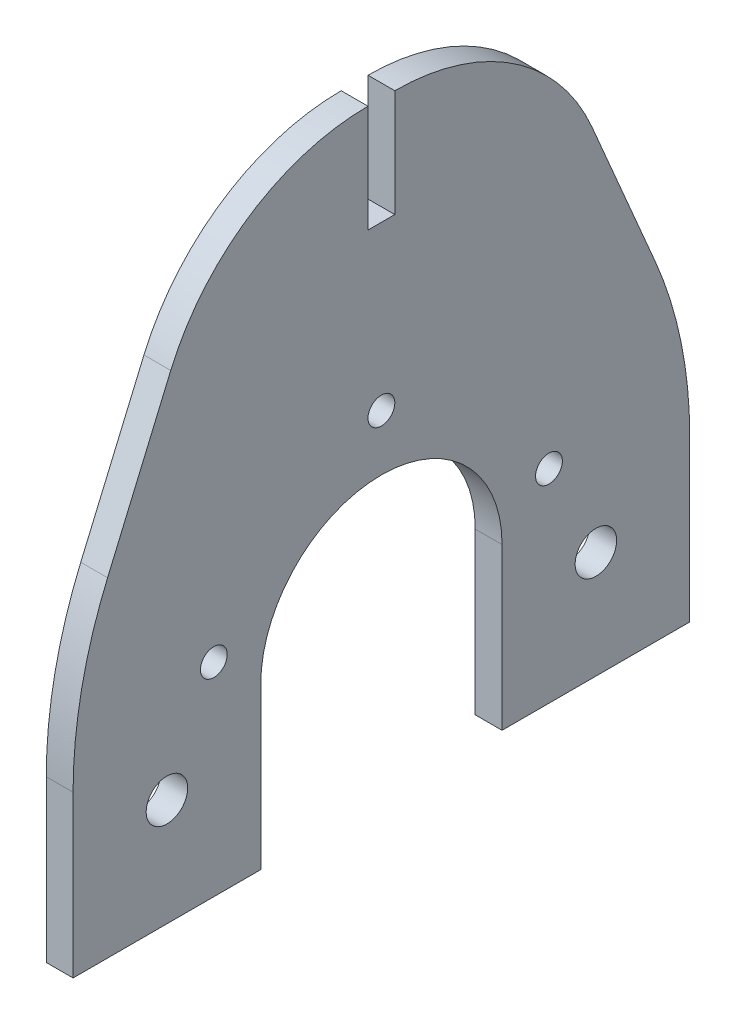
SolidWorks part; units mm, degrees
material "6061 Alloy"
ref_plane "Front Plane" through (0, 0, 0) normal (0, 0, 1) x (1, 0, 0)
ref_plane "Top Plane" through (0, 0, 0) normal (0, 1, 0) x (1, 0, 0)
ref_plane "Right Plane" through (0, 0, 0) normal (1, 0, 0) x (0, 0, -1)
sketch "Sketch1" plane through (0, 0, 0) normal (1, 0, 0) x (0, 0, -1)
  line L0 (1.5875, 52.8963) -> (1.5875, 40.1963)
  line L1 (1.5875, 40.1963) -> (-1.5875, 40.1963)
  line L2 (0, 0) -> (0, 73.524) construction
  line L3 (-1.5875, 52.8963) -> (-1.5875, 40.1963)
  line L4 (25.4, 0) -> (-25.4, 0) construction
  line L5 (24.9457, 37.4739) -> (32.429, 19.9553)
  line L6 (-24.9457, 37.4739) -> (-32.429, 19.9553)
  line L7 (36.5125, 0) -> (36.5125, -19.05)
  line L8 (36.5125, -19.05) -> (14.2875, -19.05)
  line L9 (14.2875, -19.05) -> (14.2875, 0)
  line L10 (-14.2875, 0) -> (-14.2875, -19.05)
  line L11 (-14.2875, -19.05) -> (-36.5125, -19.05)
  line L12 (-36.5125, -19.05) -> (-36.5125, 0)
  arc A0 (14.2875, 0) -> (-14.2875, 0) centre (0, 0) ccw
  arc A3 (36.5125, 0) -> (32.429, 19.9553) centre (-14.2875, 0) ccw
  arc A5 (24.9457, 37.4739) -> (1.5875, 52.8963) centre (1.5875, 27.4963) ccw
  arc A7 (-36.5125, 0) -> (-32.429, 19.9553) centre (14.2875, 0) cw
  arc A10 (-24.9457, 37.4739) -> (-1.5875, 52.8963) centre (-1.5875, 27.4963) cw
  circle A11 centre (25.4, 0) radius 2.5797 construction
  circle A12 centre (-25.4, 0) radius 2.5797 construction
  point P18 (0, 40.1963)
  point P30 (0, 0)
  dimension "D1" = 28.575
  dimension "D3" = 25.4
  dimension "D4" = 19.05
  dimension "D5" = 19.05
  dimension "D6" = 50.8
  dimension "D7" = 22.225
  dimension "D9" = 5.1594
  dimension "D2" = 3.175
  dimension "D8" = 50.8
  dimension "D12" = 12.7
extrude "Boss-Extrude1" add sketch "Sketch1" along normal blind 3.175
hole_wizard "#10 (0.1935) Diameter Hole1" positions "Sketch2" profile "Sketch3" hole size "#10" standard "ANSI Inch"
sketch "Sketch2" plane through (0, 0, 0) normal (-1, 0, 0) x (0, 0, 1)
  line L2 (-25.4, -6.35) -> (25.4, -6.35) construction
  point P0 (-25.4, -6.35)
  point P2 (25.4, -6.35)
  point P29 (0, -6.35)
  dimension "D1" = 50.8
  dimension "D2" = 6.35
sketch "Sketch3" plane through (0, -6.35, -25.4) normal (0, 1, 0) x (0, 0, 1)
  line L0 (0, 0) -> (0, 20.4786)
  line L1 (0, 20.4786) -> (2.4574, 19.002)
  line L2 (2.4574, 19.002) -> (2.4574, 0)
  line L5 (2.4574, 0) -> (0, 0)
  line L10 (0, 20.4786) -> (-2.4574, 19.002) construction
  line L11 (0, -6.35) -> (0, 107.95) construction
  dimension "Hole Dia." = 4.9149
  dimension "Hole Depth" = 19.002
  dimension "Drill Angle" = 118
sketch "Sketch4" plane through (3.175, 0, 0) normal (1, 0, 0) x (0, 0, -1)
  circle A0 centre (-19.8426, 5.0165) radius 1.5875 construction
  circle A1 centre (0, 20.8915) radius 1.5875 construction
  circle A2 centre (19.8426, 5.0165) radius 1.5875 construction
  circle A3 centre (-19.8426, 5.0165) radius 1.5875
  circle A4 centre (0, 20.8915) radius 1.5875
  circle A5 centre (19.8426, 5.0165) radius 1.5875
extrude "Cut-Extrude1" cut sketch "Sketch4" against normal through all
